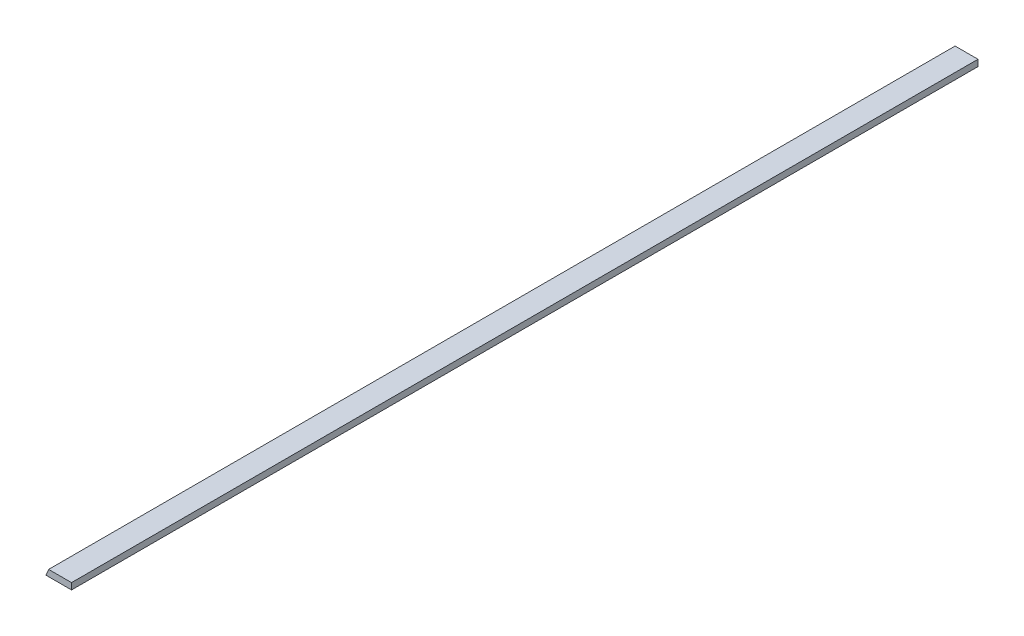
SolidWorks part; units mm, degrees
ref_plane "Front Plane" through (0, 0, 0) normal (0, 0, 1) x (1, 0, 0)
ref_plane "Top Plane" through (0, 0, 0) normal (0, 1, 0) x (1, 0, 0)
ref_plane "Right Plane" through (0, 0, 0) normal (1, 0, 0) x (0, 0, -1)
sketch "Sketch1" plane through (0, 0, 0) normal (0, 0, 1) x (1, 0, 0)
  line L0 (0, 0) -> (25.4, 0)
  line L1 (25.4, 0) -> (25.4, 6.35)
  line L2 (25.4, 6.35) -> (2.6303, 6.35)
  line L3 (2.6303, 6.35) -> (0, 0)
  dimension "D1" = 67.5
  dimension "D2" = 25.4
  dimension "D3" = 6.35
extrude "Boss-Extrude1" add sketch "Sketch1" along normal blind 901.7
